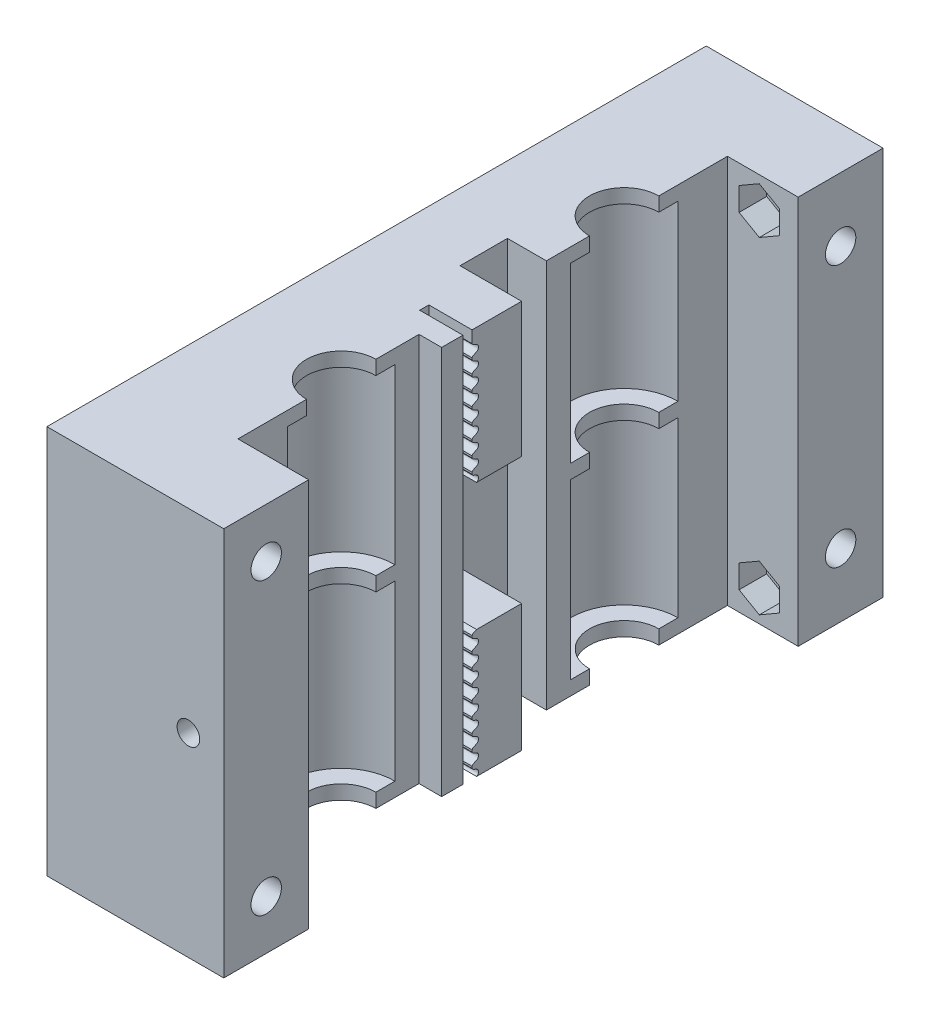
SolidWorks part; units mm, degrees
ref_plane "Front Plane" through (0, 0, 0) normal (0, 0, 1) x (1, 0, 0)
ref_plane "Top Plane" through (0, 0, 0) normal (0, 1, 0) x (1, 0, 0)
ref_plane "Right Plane" through (0, 0, 0) normal (1, 0, 0) x (0, 0, -1)
sketch "Sketch1" plane through (0, 0, 0) normal (0, 1, 0) x (1, 0, 0)
  line L0 (0, 36.6) -> (0, 43.6)
  line L1 (0, 43.6) -> (10, 43.6)
  line L2 (10, 43.6) -> (10, 55.6)
  line L3 (10, 55.6) -> (-15, 55.6)
  line L5 (-15, -37.6) -> (10, -37.6)
  line L6 (10, -37.6) -> (10, -25.6)
  line L7 (10, -25.6) -> (0, -25.6)
  line L8 (0, -25.6) -> (0, -18.6)
  line L9 (0, 21.4) -> (0, -3.4) construction
  line L10 (0, 18) -> (-5.5, 18)
  line L11 (-5.5, 18) -> (-5.5, 0)
  line L12 (-5.5, 0) -> (0, 0)
  line L24 (-15, 55.6) -> (-15, -37.6)
  line L25 (0, 0) -> (0, -3.4)
  line L26 (0, 18) -> (0, 21.4)
  arc A1 (0, 21.4) -> (0, 36.6) centre (0, 29) cw
  arc A2 (0, -18.6) -> (0, -3.4) centre (0, -11) cw
  dimension "D2" = 7.6
  dimension "D3" = 7.6
  dimension "D4" = 7
  dimension "D5" = 7
  dimension "D6" = 12
  dimension "D7" = 12
  dimension "D8" = 18
  dimension "D9" = 10
  dimension "D10" = 10
  dimension "D11" = 5.5
  dimension "D12" = 3.4
  dimension "D13" = 3.4
  dimension "D14" = 25
  dimension "D15" = 40
extrude "Boss-Extrude1" add sketch "Sketch1" along normal blind 55
sketch "Sketch2" plane through (0, 0, 0) normal (0, -1, 0) x (1, 0, 0)
  line L0 (0, 18.6) -> (0, 15.9)
  line L1 (0, 6.1) -> (0, 3.4)
  line L2 (0, -21.4) -> (0, -24.102)
  line L3 (0, -33.898) -> (0, -36.6)
  arc A0 (0, 3.4) -> (0, 18.6) centre (0, 11) cw
  arc A1 (0, 6.1) -> (0, 15.9) centre (0, 11) cw
  arc A2 (0, -36.6) -> (0, -21.4) centre (0, -29) cw
  arc A3 (0, -33.898) -> (0, -24.102) centre (0, -29) cw
  dimension "D1" = 4.9
  dimension "D2" = 4.898
extrude "Boss-Extrude2" add sketch "Sketch2" against normal blind 2
ref_plane "Plane1" through (0, 26.5, 0) normal (0, -1, 0) x (-1, 0, 0)
sketch "Sketch3" plane through (0, 26.5, 0) normal (0, -1, 0) x (-1, 0, 0)
  line L0 (0, -3.4) -> (0, -6.1)
  line L1 (0, -15.9) -> (0, -18.6)
  line L2 (0, 21.4) -> (0, 24.1)
  line L3 (0, 33.9) -> (0, 36.6)
  arc A0 (0, -18.6) -> (0, -3.4) centre (0, -11) ccw
  arc A1 (0, -15.9) -> (0, -6.1) centre (0, -11) ccw
  arc A2 (0, 36.6) -> (0, 21.4) centre (0, 29) cw
  arc A3 (0, 24.1) -> (0, 33.9) centre (0, 29) ccw
  dimension "D1" = 4.9
extrude "Boss-Extrude3" add sketch "Sketch3" against normal blind 2
ref_plane "Plane2" through (0, 53, 0) normal (0, -1, 0) x (-1, 0, 0)
sketch "Sketch4" plane through (0, 53, 0) normal (0, -1, 0) x (-1, 0, 0)
  line L0 (0, -18.6) -> (0, -15.9)
  line L1 (0, -6.1) -> (0, -3.4)
  line L2 (0, 36.6) -> (0, 33.9)
  line L3 (0, 24.1) -> (0, 21.4)
  arc A0 (0, -3.4) -> (0, -18.6) centre (0, -11) cw
  arc A1 (0, -15.9) -> (0, -6.1) centre (0, -11) ccw
  arc A2 (0, -15.9) -> (0, -6.1) centre (0, -11) ccw construction
  arc A3 (0, 21.4) -> (0, 36.6) centre (0, 29) ccw construction
  arc A5 (0, 24.1) -> (0, 33.9) centre (0, 29) ccw
  arc A6 (0, 21.4) -> (0, 36.6) centre (0, 29) ccw
  arc A7 (0, 24.1) -> (0, 33.9) centre (0, 29) ccw construction
extrude "Boss-Extrude4" add sketch "Sketch4" against normal blind 2
sketch "Sketch7" plane through (0, 55, 0) normal (0, 1, 0) x (1, 0, 0)
  line L0 (0, 0) -> (3.2, 0)
  line L1 (3.2, 0) -> (3.2, -2)
  line L2 (3.2, -2) -> (0, -2)
  line L3 (0, -6.1) -> (0, 0) construction
  line L4 (0, -2) -> (0, 0)
  dimension "D1" = 2
  dimension "D2" = 3.2
extrude "Boss-Extrude5" add sketch "Sketch7" against normal up to surface (55 mm away) up to face at (-0.6749, 0, -9)
sketch "Sketch8" plane through (0, 55, 0) normal (0, 1, 0) x (1, 0, 0)
  line L0 (0, 18) -> (0, 0) construction
  line L1 (-3.9424, 9) -> (6.0186, 9) construction
  line L2 (-5.5, 0) -> (3.2, 0)
  line L3 (3.2, 0) -> (-5.5, 0) construction
  line L4 (3.2, 0) -> (3.2, 3)
  line L5 (3.2, 3) -> (-5.5, 3)
  line L6 (-5.5, 0) -> (-5.5, 18) construction
  line L7 (-5.5, 3) -> (-5.5, 0)
  line L8 (3.2, -2) -> (3.2, 0) construction
  line L9 (-5.5, 11.3) -> (3.2, 11.3)
  line L10 (3.2, 11.3) -> (3.2, 4.3)
  line L11 (3.2, 4.3) -> (-5.5, 4.3)
  line L12 (-5.5, 4.3) -> (-5.5, 11.3)
  point P6 (0, 9)
  dimension "D1" = 3
  dimension "D2" = 7
  dimension "D3" = 1.3
extrude "Boss-Extrude6" add sketch "Sketch8" against normal up to surface (55 mm away) up to face at (-0.2443, 0, -7.7778)
sketch "Sketch11" plane through (3.2, 0, 0) normal (1, 0, 0) x (0, 0, -1)
  line L0 (1264.5675, 560.6102) -> (1262.5675, 560.6102) construction
  line L1 (4.3, 0) -> (4.3, 55) construction
  line L2 (4.2853, 45.4328) -> (4.2853, 47.4569)
  spline S0 degree 3 poles (4.2853, 47.4569) (4.284, 47.4147) (4.2867, 47.3463) (4.3158, 47.2523) (4.3712, 47.1708) (4.4771, 47.1012) (4.6041, 47.0544) (4.7214, 46.9971) (4.8254, 46.9474) (4.9241, 46.9047) (5.0186, 46.8525) (5.1086, 46.7783) (5.1561, 46.6816) (5.1905, 46.5926) (5.1913, 46.5195) (5.1931, 46.4561) (5.1891, 46.3829) (5.1871, 46.2871) (5.1399, 46.1709) (5.0494, 46.057) (4.9087, 45.9856) (4.7554, 45.916) (4.621, 45.8529) (4.5075, 45.8004) (4.4122, 45.7562) (4.3028, 45.6419) (4.2855, 45.5136) (4.2853, 45.4328) knots 0 0 0 0 0.042789 0.068472 0.09859 0.140403 0.193951 0.235463 0.272242 0.310543 0.344117 0.381404 0.42616 0.451184 0.477135 0.499165 0.515432 0.551275 0.595353 0.639476 0.695379 0.752126 0.810504 0.845135 0.878871 0.916023 1 1 1 1
  line M5 (4.3, 55) -> (4.3, 0)
  dimension "D1" = 2
extrude "Cut-Extrude4" cut sketch "Sketch11" against normal up to surface (8.7 mm away) contours S0 M5 region at (3.2, 46.4474, -4.673) up to face at (-5.5, 27.5, -3.65)
pattern_linear "LPattern1" count 24 spacing 2 along (0, -1, 0) count 4 spacing 2 along (0, 1, 0) of "Cut-Extrude4"
sketch "Sketch12" plane through (3.2, 0, 0) normal (1, 0, 0) x (0, 0, -1)
  line L0 (11.3, 0) -> (11.3, 55) construction
  line L1 (11.3, 36) -> (4.3, 36)
  line L2 (11.3, 36) -> (11.3, 18)
  line L3 (11.3, 18) -> (4.3, 18)
  line L4 (4.3, 36) -> (4.3, 18)
  dimension "D1" = 18
  dimension "D2" = 19
extrude "Cut-Extrude5" cut sketch "Sketch12" against normal up to surface (8.7 mm away) up to face at (-5.5, 27.5, -14.65)
sketch "Sketch13" plane through (0, 55, 0) normal (0, 1, 0) x (1, 0, 0)
  line L0 (-5.5, 3) -> (-2.9059, 3)
  line L1 (3.2, 3) -> (-5.5, 3) construction
  line L6 (-2.9059, 3) -> (-2.9059, 7.169)
  line L7 (-2.9059, 7.169) -> (-5.5, 7.169)
  line L8 (-5.5, 18) -> (-5.5, 0) construction
  line L9 (-5.5, 7.169) -> (-5.5, 3)
extrude "Boss-Extrude16" add sketch "Sketch13" against normal up to surface (55 mm away) up to face at (-0.409, 0, -8.1123)
sketch "Sketch14" plane through (0, 55, 0) normal (0, 1, 0) x (1, 0, 0)
  line L0 (0, 0) -> (0, -2)
  line L1 (0, -2) -> (3.2, -2)
  line L2 (3.2, -2) -> (3.2, 0)
  line L3 (3.2, -2) -> (3.2, 3) construction
  line L4 (3.2, 0) -> (0, 0)
extrude "Cut-Extrude6" cut sketch "Sketch14" against normal up to surface (55 mm away) up to face at (-0.1732, 0, -8.1123)
sketch "Sketch16" plane through (-2.9059, 0, 0) normal (1, 0, 0) x (0, 0, -1)
  line L0 (7.169, 36) -> (3, 36)
  line L1 (3, 0) -> (3, 55) construction
  line L2 (7.169, 18) -> (3, 18)
  line L3 (3, 18) -> (3, 36)
  line L4 (7.169, 36) -> (7.169, 18)
extrude "Cut-Extrude7" cut sketch "Sketch16" against normal up to surface (2.5941 mm away) up to face at (-5.5, 27.25, -11.9423)
sketch "Sketch17" plane through (-15, 0, 0) normal (-1, 0, 0) x (0, 0, 1)
  line L0 (-55.6, 55) -> (37.6, 55) construction
  line L1 (37.6, 55) -> (37.6, 0) construction
  line L2 (37.6, 0) -> (25.6, 0) construction
  line L3 (-36.6, 0) -> (-43.6, 0) construction
  line L4 (-55.6, 55) -> (-55.6, 0) construction
  circle A0 centre (31.6, 48) radius 2.15
  circle A1 centre (31.6, 7) radius 2.15
  circle A2 centre (-49.6, 9) radius 2.15
  circle A3 centre (-49.6, 46) radius 2.15
  dimension "D1" = 4.3
  dimension "D2" = 4.3
  dimension "D3" = 4.3
  dimension "D4" = 4.3
  dimension "D6" = 6
  dimension "D7" = 7
  dimension "D5" = 7
  dimension "D8" = 6
  dimension "D9" = 9
  dimension "D10" = 6
  dimension "D11" = 6
  dimension "D12" = 9
extrude "Cut-Extrude8" cut sketch "Sketch17" against normal up to surface (25 mm away) up to face at (10, 27.5, 31.6)
ref_plane "Plane3" through (-11.9, 0, 0) normal (-1, 0, 0) x (0, 0, 1)
sketch "Sketch20" plane through (-5.5, 0, 0) normal (1, 0, 0) x (0, 0, -1)
  line L0 (55.6, 55) -> (-37.6, 55) construction
  line L1 (55.6, 55) -> (55.6, 0) construction
  circle A0 centre (9, 27.5) radius 2.7
  dimension "D1" = 5.4
  dimension "D2" = 27.5
  dimension "D3" = 46.6
extrude "Cut-Extrude9" cut sketch "Sketch20" against normal up to surface (9.5 mm away) up to face at (-15, 46, -47.45)
sketch "Sketch21" plane through (0, 0, -43.6) normal (0, 0, 1) x (1, 0, 0)
  line L0 (10, 55) -> (10, 0) construction
  line L1 (4.5, 47.3091) -> (7.35, 48.9546)
  line L2 (7.35, 48.9546) -> (7.35, 52.2454)
  line L3 (7.35, 52.2454) -> (4.5, 53.8909)
  line L4 (4.5, 53.8909) -> (1.65, 52.2454)
  line L5 (1.65, 52.2454) -> (1.65, 48.9546)
  line L6 (1.65, 48.9546) -> (4.5, 47.3091)
  line L7 (0, 55) -> (10, 55) construction
  circle A0 centre (4.5, 50.6) radius 2.85 construction
  point P10 (4.4845, 50.4524)
  point P11 (4.4439, 50.5663)
  dimension "D2" = 4.4
  dimension "D3" = 5.5
  dimension "D1" = 5.7
ref_plane "Plane4" through (0, 27.5, 0) normal (0, 1, 0) x (1, 0, 0)
extrude "Cut-Extrude10" cut sketch "Sketch21" against normal blind 3.9
sketch "Sketch23" plane through (0, 0, -47.5) normal (0, 0, 1) x (1, 0, 0)
  line L0 (0, 55) -> (10, 55) construction
  line L1 (10, 55) -> (10, 0) construction
  circle A0 centre (4.5, 50.6) radius 1.6
  dimension "D1" = 3.2
  dimension "D2" = 4.4
  dimension "D3" = 5.5
extrude "Cut-Extrude11" cut sketch "Sketch23" against normal up to surface (8.1 mm away) up to face at (-2.5, 27.5, -55.6)
mirror "Mirror1" about plane through (0, 27.5, 0) normal (0, 1, 0) of "Cut-Extrude11", "Cut-Extrude10"
sketch "Sketch26" plane through (0, 0, 25.6) normal (0, 0, -1) x (-1, 0, 0)
  line L0 (-10, 55) -> (-10, 0) construction
  line L1 (-5, 24.2091) -> (-2.15, 25.8546)
  line L2 (-2.15, 25.8546) -> (-2.15, 29.1454)
  line L3 (-2.15, 29.1454) -> (-5, 30.7909)
  line L4 (-5, 30.7909) -> (-7.85, 29.1454)
  line L5 (-7.85, 29.1454) -> (-7.85, 25.8546)
  line L6 (-7.85, 25.8546) -> (-5, 24.2091)
  line L7 (-10, 0) -> (0, 0) construction
  circle A0 centre (-5, 27.5) radius 2.85 construction
  point P10 (0, 0)
  point P12 (0, 0)
  point P16 (-4.6123, 25.7131)
  dimension "D1" = 27.5
  dimension "D2" = 5
  dimension "D3" = 5.7
extrude "Cut-Extrude12" cut sketch "Sketch26" against normal blind 4
sketch "Sketch27" plane through (0, 0, 29.6) normal (0, 0, -1) x (-1, 0, 0)
  line L0 (-10, 55) -> (-10, 0) construction
  line L1 (-10, 55) -> (0, 55) construction
  circle A0 centre (-5, 27.5) radius 1.6
  dimension "D3" = 3.2
  dimension "D1" = 5
  dimension "D2" = 27.5
extrude "Cut-Extrude13" cut sketch "Sketch27" against normal up to surface (8 mm away) up to face at (-2.5, 27.5, 37.6)
sketch "Sketch28" plane through (-15, 0, 0) normal (-1, 0, 0) x (0, 0, 1)
  line L0 (-55.6, 55) -> (-55.6, 0) construction
  line L1 (-45.95, 11.1073) -> (-49.6, 13.2147)
  line L2 (-49.6, 13.2147) -> (-53.25, 11.1073)
  line L3 (-53.25, 11.1073) -> (-53.25, 6.8927)
  line L4 (-53.25, 6.8927) -> (-49.6, 4.7853)
  line L5 (-49.6, 4.7853) -> (-45.95, 6.8927)
  line L6 (-45.95, 6.8927) -> (-45.95, 11.1073)
  circle A0 centre (-49.6, 9) radius 3.65 construction
  dimension "D1" = 7.3
extrude "Cut-Extrude14" cut sketch "Sketch28" against normal blind 4
pattern_linear "LPattern4" count 2 spacing 37 along (0, 1, 0) of "Cut-Extrude14"
sketch "Sketch29" plane through (-15, 0, 0) normal (-1, 0, 0) x (0, 0, 1)
  line L0 (37.6, 55) -> (37.6, 0) construction
  line L1 (31.6, 11.2147) -> (27.95, 9.1073)
  line L2 (27.95, 9.1073) -> (27.95, 4.8927)
  line L3 (27.95, 4.8927) -> (31.6, 2.7853)
  line L4 (31.6, 2.7853) -> (35.25, 4.8927)
  line L5 (35.25, 4.8927) -> (35.25, 9.1073)
  line L6 (35.25, 9.1073) -> (31.6, 11.2147)
  circle A0 centre (31.6, 7) radius 3.65 construction
  point P11 (35.25, 7)
  dimension "D1" = 7.3
extrude "Cut-Extrude15" cut sketch "Sketch29" against normal blind 4
pattern_linear "LPattern5" count 2 spacing 41 along (0, 1, 0) of "Cut-Extrude15"
ref_plane "Plane5" through (0, 0, -53.7) normal (0, 0, -1) x (-1, 0, 0)
sketch "Sketch30" plane through (0, 0, -53.7) normal (0, 0, -1) x (-1, 0, 0)
  circle A0 centre (-4.5, 50.6) radius 1.6 construction
  circle A1 centre (-4.5, 50.6) radius 1.6
sketch "Sketch31" plane through (0, 0, -55.6) normal (0, 0, -1) x (-1, 0, 0)
  circle A0 centre (-4.5, 50.6) radius 3.375
  dimension "D1" = 6.75
loft "Cut-Loft4" cut profiles "Sketch31", "Sketch30" connector at (1.8502, 48.5097, -55.6) connector at (5.3463, 51.9579, -53.7)
pattern_linear "LPattern6" count 2 spacing 46.6 along (0, -1, 0) of "Cut-Loft4"
